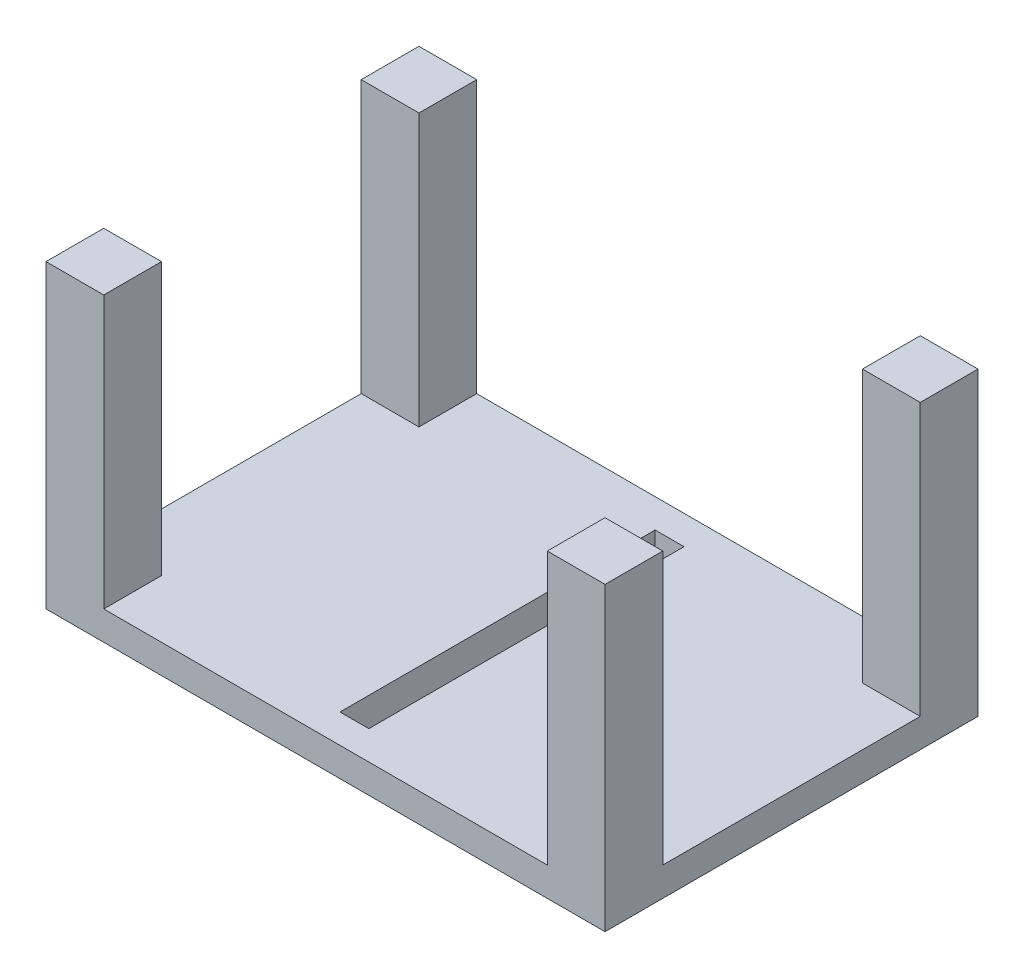
SolidWorks part; units mm, degrees
ref_plane "Front Plane" through (0, 0, 0) normal (0, 0, 1) x (1, 0, 0)
ref_plane "Top Plane" through (0, 0, 0) normal (0, 1, 0) x (1, 0, 0)
ref_plane "Right Plane" through (0, 0, 0) normal (1, 0, 0) x (0, 0, -1)
sketch "Sketch1" plane through (0, 0, 0) normal (0, 1, 0) x (1, 0, 0)
  line L1 (-61.468, -41.0083) -> (61.468, -41.0083)
  line L2 (-61.468, -41.0083) -> (-61.468, 41.0083)
  line L3 (-61.468, 41.0083) -> (61.468, 41.0083)
  line L4 (61.468, -41.0083) -> (61.468, 41.0083)
  line L5 (-61.468, -41.0083) -> (61.468, 41.0083) construction
  line L6 (-61.468, 41.0083) -> (61.468, -41.0083) construction
  point P0 (0, 0)
  dimension "D1" = 82.0166
  dimension "D2" = 122.936
extrude "Boss-Extrude3" add sketch "Sketch1" along normal blind 6.35
sketch "Sketch2" plane through (0, 6.35, 0) normal (0, 1, 0) x (1, 0, 0)
  line L0 (0, -55) -> (0, 55) construction
  line L1 (-61.468, 41.0083) -> (-48.768, 41.0083)
  line L2 (-61.468, 41.0083) -> (-61.468, 28.3083)
  line L3 (-61.468, 28.3083) -> (-48.768, 28.3083)
  line L4 (-48.768, 41.0083) -> (-48.768, 28.3083)
  line L5 (-61.468, 41.0083) -> (-48.768, 28.3083) construction
  line L6 (-61.468, 28.3083) -> (-48.768, 41.0083) construction
  line L7 (61.468, 28.3083) -> (48.768, 28.3083)
  line L8 (48.768, 41.0083) -> (48.768, 28.3083)
  line L9 (61.468, 41.0083) -> (48.768, 41.0083)
  line L10 (61.468, 41.0083) -> (61.468, 28.3083)
  line L11 (61.468, 28.3083) -> (48.768, 41.0083) construction
  line L12 (61.468, 41.0083) -> (48.768, 28.3083) construction
  line L13 (-55, 0) -> (55, 0) construction
  line L14 (61.468, -41.0083) -> (61.468, -28.3083)
  line L15 (61.468, -41.0083) -> (48.768, -41.0083)
  line L16 (48.768, -41.0083) -> (48.768, -28.3083)
  line L17 (61.468, -28.3083) -> (48.768, -28.3083)
  line L18 (-61.468, -28.3083) -> (-48.768, -28.3083)
  line L19 (-48.768, -41.0083) -> (-48.768, -28.3083)
  line L20 (-61.468, -41.0083) -> (-48.768, -41.0083)
  line L21 (-61.468, -41.0083) -> (-61.468, -28.3083)
  point P4 (-55.118, 34.6583)
  point P12 (55.118, 34.6583)
  dimension "D1" = 12.7
extrude "Boss-Extrude4" add sketch "Sketch2" along normal blind 59.8
sketch "Sketch3" plane through (0, 0, 0) normal (0, -1, 0) x (1, 0, 0)
  line L0 (0, 41.0083) -> (3.175, 41.0083) construction
  line L1 (-61.468, 41.0083) -> (61.468, 41.0083) construction
  line L2 (0, -41.0083) -> (-3.175, -41.0083) construction
  line L3 (61.468, -41.0083) -> (-61.468, -41.0083) construction
  line L4 (-3.175, -41.0083) -> (-3.175, -34.6583) construction
  line L5 (3.175, 41.0083) -> (3.175, 34.6583) construction
  line L7 (3.175, 34.6583) -> (-3.175, 34.6583)
  line L8 (3.175, 34.6583) -> (3.175, -34.6583)
  line L9 (3.175, -34.6583) -> (-3.175, -34.6583)
  line L10 (-3.175, 34.6583) -> (-3.175, -34.6583)
  line L11 (3.175, 34.6583) -> (-3.175, -34.6583) construction
  line L12 (3.175, -34.6583) -> (-3.175, 34.6583) construction
  point P13 (0, 0)
  dimension "D1" = 3.175
  dimension "D2" = 3.175
  dimension "D3" = 6.35
  dimension "D4" = 6.35
extrude "Cut-Extrude1" cut sketch "Sketch3" against normal up to next contours L8 L7 L10 L9
